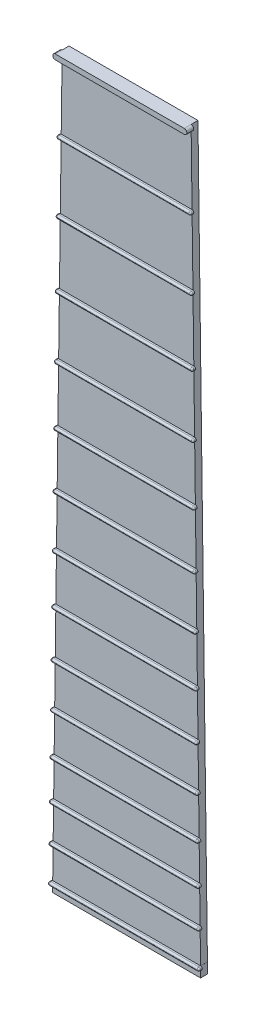
SolidWorks part; units mm, degrees
ref_plane "Front Plane" through (0, 0, 0) normal (0, 0, 1) x (1, 0, 0)
ref_plane "Top Plane" through (0, 0, 0) normal (0, 1, 0) x (1, 0, 0)
ref_plane "Right Plane" through (0, 0, 0) normal (1, 0, 0) x (0, 0, -1)
sketch "Sketch1" plane through (0, 0, 0) normal (0, 0, 1) x (1, 0, 0)
  line L0 (-19.0286, 111.6852) -> (19.0286, 111.6852)
  line L1 (-18.75, 133.0152) -> (18.75, 133.0152)
  line L2 (-21.5, -77.5448) -> (21.5, -77.5448)
  line L3 (-18.75, 133.0152) -> (-21.5, -77.5448)
  line L4 (-21.5, -77.5448) -> (-21.4292, -77.5448)
  line L5 (21.5, -77.5448) -> (18.75, 133.0152)
  line L6 (-19.2915, 91.5552) -> (19.2915, 91.5552)
  line L7 (-19.5396, 72.5552) -> (19.5396, 72.5552)
  line L8 (-19.7722, 54.7511) -> (19.7722, 54.7511)
  line L9 (-19.9931, 37.8311) -> (19.9931, 37.8311)
  line L10 (-20.2017, 21.8611) -> (20.2017, 21.8611)
  line L11 (-20.3987, 6.7811) -> (20.3987, 6.7811)
  line L12 (-20.5845, -7.4489) -> (20.5845, -7.4489)
  line L13 (-20.7599, -20.8789) -> (20.7599, -20.8789)
  line L14 (-20.9255, -33.5589) -> (20.9255, -33.5589)
  line L15 (-21.0819, -45.5289) -> (21.0819, -45.5289)
  line L16 (-21.2294, -56.8289) -> (21.2294, -56.8289)
  line L17 (-21.3687, -67.4889) -> (21.3687, -67.4889)
  line L18 (-21.5001, -77.5489) -> (21.5001, -77.5489)
  line L19 (0, 133.0152) -> (0, -299.9849) construction
  line L20 (-20.8375, -155.4448) -> (20.8375, -155.4448) [skipped]
  line L21 (-20.7, -136.4448) -> (20.7, -136.4448) [skipped]
  line L22 (-20.5625, -117.4448) -> (20.5625, -117.4448) [skipped]
  line L23 (-20.425, -98.4448) -> (20.425, -98.4448) [skipped]
  line L24 (-20.2875, -79.4448) -> (20.2875, -79.4448) [skipped]
  line L25 (-20.15, -60.4448) -> (20.15, -60.4448) [skipped]
  line L26 (-20.0125, -41.4448) -> (20.0125, -41.4448) [skipped]
  line L27 (-19.875, -22.4448) -> (19.875, -22.4448) [skipped]
  line L28 (-19.7375, -3.4448) -> (19.7375, -3.4448) [skipped]
  line L29 (-19.6, 15.5552) -> (19.6, 15.5552) [skipped]
  line L30 (-19.4625, 34.5552) -> (19.4625, 34.5552) [skipped]
  line L31 (-19.325, 53.5552) -> (19.325, 53.5552) [skipped]
  line L32 (-64.8106, -246.6689) -> (92.0858, -246.6689)
  line L33 (-18.75, 133.0152) -> (-18.75, 135.5925)
  line L34 (-18.75, 135.5925) -> (18.75, 135.5925)
  line L35 (18.75, 135.5925) -> (18.75, 133.0152)
  line L36 (-21.5001, -77.5489) -> (-21.5001, -80.6002)
  line L37 (-21.5001, -80.6002) -> (21.5001, -80.6002)
  line L38 (21.5001, -80.6002) -> (21.5001, -77.5489)
  line L39 (21.5001, -77.5489) -> (22.4086, -76.742)
  point P4 (0, 0)
  point P6 (0, 133.0152)
  point P10 (0, -77.5448)
  point P67 (-14.25, 135.5925)
  point P68 (-4.75, 135.5925)
  point P69 (4.75, 135.5925)
  point P70 (14.25, 135.5925)
  dimension "D1" = 37.5
  dimension "D2" = 43
  dimension "D4" = 21.33
  dimension "D5" = 20.13
  dimension "D6" = 210.56
  dimension "D7" = 19
  dimension "D8" = 17.8041
  dimension "D9" = 16.92
  dimension "D10" = 15.97
  dimension "D11" = 15.08
  dimension "D12" = 14.23
  dimension "D13" = 13.43
  dimension "D14" = 12.68
  dimension "D15" = 11.97
  dimension "D16" = 11.3
  dimension "D17" = 10.66
  dimension "D18" = 10.06
  dimension "D19" = 189.84
  dimension "D20" = 9.5
  dimension "D21" = 9.5
  dimension "D22" = 9.5
  dimension "D23" = 4.5
  dimension "D3" = 14
extrude "Boss-Extrude1" add sketch "Sketch1" against normal blind 2 contours L19 L18 L36 L37 | L18 L19 L37 L38 | L2 L5 L1 L3 region at (10.75, -79.0745, 0) region at (-10.75, -79.0745, 0)
sketch "Sketch2" plane through (0, 0, 0) normal (0, 0, 1) x (1, 0, 0)
  line L0 (-21.5, -77.5448) -> (21.5, -77.5448) construction
  line L1 (-21.3687, -67.4889) -> (21.3687, -67.4889) construction
  line L2 (-21.2294, -56.8289) -> (21.2294, -56.8289) construction
  line L3 (-20.9255, -33.5589) -> (20.9255, -33.5589) construction
  line L4 (-21.0819, -45.5289) -> (21.0819, -45.5289) construction
  line L5 (-20.7599, -20.8789) -> (20.7599, -20.8789) construction
  line L6 (-20.5845, -7.4489) -> (20.5845, -7.4489) construction
  line L7 (-20.3987, 6.7811) -> (20.3987, 6.7811) construction
  line L8 (-20.2017, 21.8611) -> (20.2017, 21.8611) construction
  line L9 (-19.9931, 37.8311) -> (19.9931, 37.8311) construction
  line L10 (-19.7722, 54.7511) -> (19.7722, 54.7511) construction
  line L11 (-19.5396, 72.5552) -> (19.5396, 72.5552) construction
  line L12 (-19.2915, 91.5552) -> (19.2915, 91.5552) construction
  line L13 (-19.0286, 111.6852) -> (19.0286, 111.6852) construction
  line L14 (-21.5, -77.5448) -> (21.5, -77.5448)
  line L15 (-21.3687, -67.4889) -> (21.3687, -67.4889)
  line L16 (-21.2294, -56.8289) -> (21.2294, -56.8289)
  line L17 (-20.9255, -33.5589) -> (20.9255, -33.5589)
  line L18 (-21.0819, -45.5289) -> (21.0819, -45.5289)
  line L19 (-20.7599, -20.8789) -> (20.7599, -20.8789)
  line L20 (-20.5845, -7.4489) -> (20.5845, -7.4489)
  line L21 (-20.3987, 6.7811) -> (20.3987, 6.7811)
  line L22 (-20.2017, 21.8611) -> (20.2017, 21.8611)
  line L23 (-19.9931, 37.8311) -> (19.9931, 37.8311)
  line L24 (-19.7722, 54.7511) -> (19.7722, 54.7511)
  line L25 (-19.5396, 72.5552) -> (19.5396, 72.5552)
  line L26 (-19.2915, 91.5552) -> (19.2915, 91.5552)
  line L27 (-19.0286, 111.6852) -> (19.0286, 111.6852)
  line L28 (-21.5, -78.5448) -> (21.5, -78.5448)
  line L29 (-21.3687, -68.4889) -> (21.3687, -68.4889)
  line L30 (-21.2294, -57.8289) -> (21.2294, -57.8289)
  line L31 (-20.9255, -34.5589) -> (20.9255, -34.5589)
  line L32 (-21.0819, -46.5289) -> (21.0819, -46.5289)
  line L33 (-20.7599, -21.8789) -> (20.7599, -21.8789)
  line L34 (-20.5845, -8.4489) -> (20.5845, -8.4489)
  line L35 (-20.3987, 5.7811) -> (20.3987, 5.7811)
  line L36 (-20.2017, 20.8611) -> (20.2017, 20.8611)
  line L37 (-19.9931, 36.8311) -> (19.9931, 36.8311)
  line L38 (-19.7722, 53.7511) -> (19.7722, 53.7511)
  line L39 (-19.5396, 71.5552) -> (19.5396, 71.5552)
  line L40 (-19.2915, 90.5552) -> (19.2915, 90.5552)
  line L41 (-19.0286, 110.6852) -> (19.0286, 110.6852)
  line L42 (-18.75, 133.0152) -> (18.75, 133.0152)
  line L43 (-18.75, 132.0152) -> (18.75, 132.0152)
  arc A0 (-21.5, -77.5448) -> (-21.5, -78.5448) centre (-21.5, -78.0448) ccw
  arc A1 (21.5, -77.5448) -> (21.5, -78.5448) centre (21.5, -78.0448) cw
  arc A2 (-21.3687, -67.4889) -> (-21.3687, -68.4889) centre (-21.3687, -67.9889) ccw
  arc A3 (21.3687, -67.4889) -> (21.3687, -68.4889) centre (21.3687, -67.9889) cw
  arc A4 (-21.2294, -56.8289) -> (-21.2294, -57.8289) centre (-21.2294, -57.3289) ccw
  arc A5 (21.2294, -56.8289) -> (21.2294, -57.8289) centre (21.2294, -57.3289) cw
  arc A6 (-20.9255, -33.5589) -> (-20.9255, -34.5589) centre (-20.9255, -34.0589) ccw
  arc A7 (20.9255, -33.5589) -> (20.9255, -34.5589) centre (20.9255, -34.0589) cw
  arc A8 (-21.0819, -45.5289) -> (-21.0819, -46.5289) centre (-21.0819, -46.0289) ccw
  arc A9 (21.0819, -45.5289) -> (21.0819, -46.5289) centre (21.0819, -46.0289) cw
  arc A10 (-20.7599, -20.8789) -> (-20.7599, -21.8789) centre (-20.7599, -21.3789) ccw
  arc A11 (20.7599, -20.8789) -> (20.7599, -21.8789) centre (20.7599, -21.3789) cw
  arc A12 (-20.5845, -7.4489) -> (-20.5845, -8.4489) centre (-20.5845, -7.9489) ccw
  arc A13 (20.5845, -7.4489) -> (20.5845, -8.4489) centre (20.5845, -7.9489) cw
  arc A14 (-20.3987, 6.7811) -> (-20.3987, 5.7811) centre (-20.3987, 6.2811) ccw
  arc A15 (20.3987, 6.7811) -> (20.3987, 5.7811) centre (20.3987, 6.2811) cw
  arc A16 (-20.2017, 21.8611) -> (-20.2017, 20.8611) centre (-20.2017, 21.3611) ccw
  arc A17 (20.2017, 21.8611) -> (20.2017, 20.8611) centre (20.2017, 21.3611) cw
  arc A18 (-19.9931, 37.8311) -> (-19.9931, 36.8311) centre (-19.9931, 37.3311) ccw
  arc A19 (19.9931, 37.8311) -> (19.9931, 36.8311) centre (19.9931, 37.3311) cw
  arc A20 (-19.7722, 54.7511) -> (-19.7722, 53.7511) centre (-19.7722, 54.2511) ccw
  arc A21 (19.7722, 54.7511) -> (19.7722, 53.7511) centre (19.7722, 54.2511) cw
  arc A22 (-19.5396, 72.5552) -> (-19.5396, 71.5552) centre (-19.5396, 72.0552) ccw
  arc A23 (19.5396, 72.5552) -> (19.5396, 71.5552) centre (19.5396, 72.0552) cw
  arc A24 (-19.2915, 91.5552) -> (-19.2915, 90.5552) centre (-19.2915, 91.0552) ccw
  arc A25 (19.2915, 91.5552) -> (19.2915, 90.5552) centre (19.2915, 91.0552) cw
  arc A26 (-19.0286, 111.6852) -> (-19.0286, 110.6852) centre (-19.0286, 111.1852) ccw
  arc A27 (19.0286, 111.6852) -> (19.0286, 110.6852) centre (19.0286, 111.1852) cw
  arc A28 (-18.75, 133.0152) -> (-18.75, 132.0152) centre (-18.75, 132.5152) ccw
  arc A29 (18.75, 133.0152) -> (18.75, 132.0152) centre (18.75, 132.5152) cw
  dimension "D1" = 1
  dimension "D2" = 1
extrude "Boss-Extrude2" add sketch "Sketch2" along normal blind 1
sketch "Sketch3" plane through (0, 0, 0) normal (0, 0, 1) x (1, 0, 0)
  line L0 (-18.75, 133.0152) -> (18.75, 133.0152) construction
  line L2 (-18.75, 133.0152) -> (18.75, 133.0152)
  line L3 (-18.7696, 131.5152) -> (18.7696, 131.5152)
  line L4 (-18.75, 133.0152) -> (-21.5, -77.5448) construction
  line L5 (21.5, -77.5448) -> (18.75, 133.0152) construction
  arc A2 (-18.75, 133.0152) -> (-18.7696, 131.5152) centre (-18.733, 132.2648) ccw
  arc A3 (18.75, 133.0152) -> (18.7696, 131.5152) centre (18.75, 132.2651) cw
  dimension "D1" = 1.5
extrude "Boss-Extrude3" add sketch "Sketch3" along normal blind 2
fillet "Fillet1" radius 0.5 4 edges at (0, 111.6852, 1) (19.5286, 111.1852, 1) (0, 110.6852, 1) (-19.5286, 111.1852, 1)
fillet "Fillet2" radius 0.5 48 edges at (0, -45.5289, 1) (21.5819, -46.0289, 1) (0, -46.5289, 1) (-21.5819, -46.0289, 1) (0, -67.4889, 1) (21.8687, -67.9889, 1) (0, -68.4889, 1) (-21.8687, -67.9889, 1) (0, -56.8289, 1) (21.7294, -57.3289, 1) (0, -57.8289, 1) (-21.7294, -57.3289, 1) (0, -33.5589, 1) (21.4255, -34.0589, 1) (0, -34.5589, 1) (-21.4255, -34.0589, 1) (0, -20.8789, 1) (21.2599, -21.3789, 1) (0, -21.8789, 1) (-21.2599, -21.3789, 1) (0, -7.4489, 1) (21.0845, -7.9489, 1) (0, -8.4489, 1) (-21.0845, -7.9489, 1) (0, 6.7811, 1) (20.8987, 6.2811, 1) (0, 5.7811, 1) (-20.8987, 6.2811, 1) (0, 21.8611, 1) (20.7017, 21.3611, 1) (0, 20.8611, 1) (-20.7017, 21.3611, 1) (0, 37.8311, 1) (20.4931, 37.3311, 1) (0, 36.8311, 1) (-20.4931, 37.3311, 1) (0, 54.7511, 1) (20.2722, 54.2511, 1) (0, 53.7511, 1) (-20.2722, 54.2511, 1) (0, 72.5552, 1) (20.0396, 72.0552, 1) (0, 71.5552, 1) (-20.0396, 72.0552, 1) (0, 91.5552, 1) (19.7915, 91.0552, 1) (0, 90.5552, 1) (-19.7915, 91.0552, 1)
fillet "Fillet3" radius 0.5 4 edges at (0, -77.5448, 1) (22, -78.0448, 1) (0, -78.5448, 1) (-22, -78.0448, 1)
